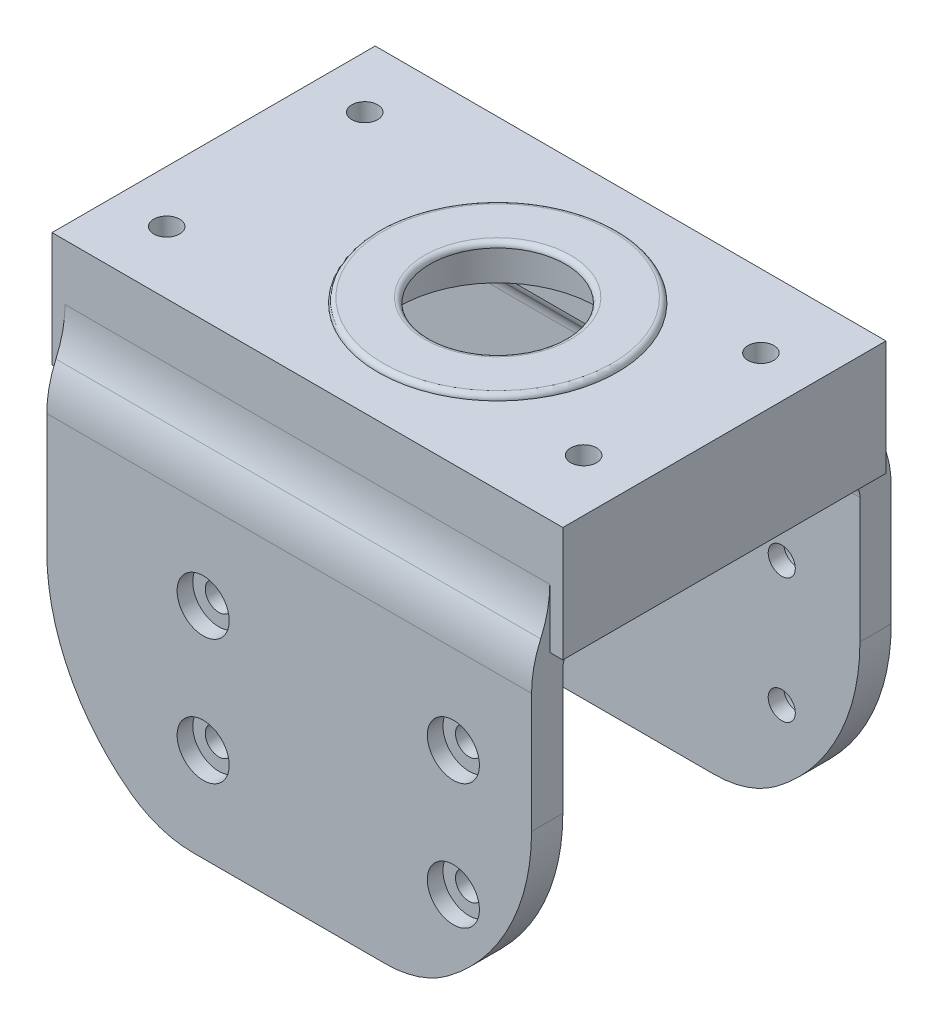
SolidWorks part; units mm, degrees
ref_plane "Front Plane" through (0, 0, 0) normal (0, 0, 1) x (1, 0, 0)
ref_plane "Top Plane" through (0, 0, 0) normal (0, 1, 0) x (1, 0, 0)
ref_plane "Right Plane" through (0, 0, 0) normal (1, 0, 0) x (0, 0, -1)
sketch "Sketch1" plane through (0, 0, 0) normal (0, 1, 0) x (1, 0, 0)
  line L0 (-24.5, 15.5) -> (24.5, 15.5)
  line L1 (-22.5, -13.5) -> (22.5, -13.5)
  line L2 (-22.5, -13.5) -> (-22.5, 13.5)
  line L3 (-22.5, 13.5) -> (22.5, 13.5)
  line L4 (22.5, -13.5) -> (22.5, 13.5)
  line L5 (-22.5, -13.5) -> (22.5, 13.5) construction
  line L6 (-22.5, 13.5) -> (22.5, -13.5) construction
  line L7 (24.5, -15.5) -> (24.5, 15.5)
  line L8 (-24.5, -15.5) -> (24.5, -15.5)
  line L9 (-24.5, -15.5) -> (-24.5, 15.5)
  circle A0 centre (2.75, 0) radius 9.475
  circle A1 centre (-19.5, 9.5) radius 1.24
  circle A2 centre (-19.5, -9.5) radius 1.24
  circle A3 centre (19.5, -8.5) radius 1.24
  circle A4 centre (19.5, 8.5) radius 1.24
  point P0 (0, 0)
  dimension "D4" = 18.95
  dimension "D6" = 2.48
  dimension "D1" = 45
  dimension "D2" = 27
  dimension "D5" = 25.25
  dimension "D7" = 3
  dimension "D8" = 4
  dimension "D9" = 4
  dimension "D10" = 3
  dimension "D11" = 5
  dimension "D12" = 5
  dimension "D3" = 2
extrude "Boss-Extrude1" add sketch "Sketch1" against normal blind 5 contours L1 L4 L3 L2 A0 region at (-21.9752, 0, 0)
extrude "Boss-Extrude2" add sketch "Sketch1<3>" against normal blind 11 contours L9 L8 L7 L0 L4 L1 L2 L3 region at (0, 0, -14.9202)
sketch "Sketch1<3>" plane through (0, 0, 0) normal (0, 1, 0) x (1, 0, 0) same geometry as "Sketch1"
sketch "Sketch2" plane through (0, -11, 0) normal (0, -1, 0) x (1, 0, 0)
  line L0 (-26.25, 17.25) -> (26.25, 17.25)
  line L1 (-23.25, -14.25) -> (23.25, -14.25)
  line L2 (-23.25, -14.25) -> (-23.25, 14.25)
  line L3 (-23.25, 14.25) -> (23.25, 14.25)
  line L4 (23.25, -14.25) -> (23.25, 14.25)
  line L5 (-23.25, -14.25) -> (23.25, 14.25) construction
  line L6 (-23.25, 14.25) -> (23.25, -14.25) construction
  line L7 (26.25, -17.25) -> (26.25, 17.25)
  line L8 (-26.25, -17.25) -> (26.25, -17.25)
  line L9 (-26.25, -17.25) -> (-26.25, 17.25)
  line L10 (-23.25, 14.25) -> (-23.25, 17.25)
  line L11 (23.25, 14.25) -> (23.25, 17.25)
  line L12 (23.25, -14.25) -> (23.25, -17.25)
  line L13 (-23.25, -14.25) -> (-23.25, -17.25)
  line L14 (-22.5, 13.5) -> (22.5, 13.5) construction
  line L15 (-15, 13.5) -> (15, 13.5)
  line L16 (-15, 13.5) -> (-15, 11.5)
  line L17 (-15, 11.5) -> (15, 11.5)
  line L18 (15, 13.5) -> (15, 11.5)
  line L19 (-22.5, -13.5) -> (22.5, -13.5) construction
  line L20 (-15, -13.5) -> (15, -13.5)
  line L21 (-15, -13.5) -> (-15, -11.5)
  line L22 (-15, -11.5) -> (15, -11.5)
  line L23 (15, -13.5) -> (15, -11.5)
  point P0 (0, 0)
  point P20 (0, 11.5)
  line M4 (-24.5, -15.5) -> (24.5, -15.5)
  line M6 (24.5, 15.5) -> (-24.5, 15.5)
  line M8 (22.5, -13.5) -> (-22.5, -13.5)
  line M10 (-22.5, 13.5) -> (22.5, 13.5)
  dimension "D1" = 46.5
  dimension "D2" = 28.5
  dimension "D4" = 30
  dimension "D5" = 2
  dimension "D3" = 3
extrude "Boss-Extrude3" add sketch "Sketch2" along normal blind 34 contours L11 L0 L10 M6 | L3 L11 L10 M6 | L1 L13 L12 M4 | L13 L8 L12 M4 region at (0, -11, 16.375) region at (0, -11, 14.875) region at (0, -11, -16.375) region at (0, -11, -14.875)
extrude "Boss-Extrude4" add sketch "Sketch2<4>" against normal up to next from offset 2 contours L18 L16 L17 M10 | L23 L22 L21 M8 region at (0, -11, 12.5) region at (0, -11, -12.5) offset against normal yes
sketch "Sketch2<4>" plane through (0, -11, 0) normal (0, -1, 0) x (1, 0, 0) same geometry as "Sketch2"
sketch "Sketch3" plane through (0, 0, -17.25) normal (0, 0, -1) x (-1, 0, 0)
  line L0 (23.25, -45) -> (23.25, -11) construction
  line L1 (23.25, -11) -> (-23.25, -11) construction
  circle A0 centre (-15.75, -22) radius 1.3
  circle A1 centre (8.25, -22) radius 1.3
  circle A2 centre (8.25, -34) radius 1.3
  circle A3 centre (-15.75, -34) radius 1.3
  circle A4 centre (-15.75, -22) radius 2.5
  circle A5 centre (-15.75, -34) radius 2.5
  circle A6 centre (8.25, -34) radius 2.5
  circle A7 centre (8.25, -22) radius 2.5
  dimension "D1" = 2.6
  dimension "D6" = 5
  dimension "D2" = 15
  dimension "D3" = 24
  dimension "D4" = 11
  dimension "D5" = 12
extrude "Cut-Extrude2" cut sketch "Sketch3" against normal through all contours A0 | A1 | A2 | A3 region at (15.75, -22, -17.25) region at (-8.25, -22, -17.25) region at (-8.25, -34, -17.25) region at (15.75, -34, -17.25)
extrude "Cut-Extrude3" cut sketch "Sketch3<3>" against normal blind 1.5
sketch "Sketch3<3>" plane through (0, 0, -17.25) normal (0, 0, -1) x (-1, 0, 0) same geometry as "Sketch3"
mirror "Mirror1" about plane through (0, 0, 0) normal (0, 0, 1) of "Cut-Extrude3"
fillet "Fillet3" radius 10 2 edges at (0, -11, -15.5) (0, -11, 15.5)
fillet "Fillet4" radius 10 2 edges at (0, -11, 17.25) (0, -11, -17.25)
fillet "Fillet5" radius 2 2 edges at (0, -11, 14.25) (0, -11, -14.25)
fillet "Fillet6" radius 2 2 edges at (0, -11.4388, -13.5) (0, -11.4388, 13.5)
fillet "Fillet7" radius 20 4 edges at (23.25, -45, 15.75) (-23.25, -45, 15.75) (-23.25, -45, -15.75) (23.25, -45, -15.75)
sketch "Sketch4" plane through (0, 0, 0) normal (0, 1, 0) x (1, 0, 0)
  circle A1 centre (2.75, 0) radius 6.5
  circle A2 centre (2.75, 0) radius 11.475
  circle A3 centre (2.75, 0) radius 11.475
  dimension "D2" = 13
  dimension "D1" = 2
extrude "Boss-Extrude5" add sketch "Sketch4" along normal blind 0.5
fillet "Fillet8" radius 0.5 2 edges at (2.75, 0.5, 11.475) (2.75, 0.5, 6.5)
sketch "Sketch5" plane through (0, 0, -17.25) normal (0, 0, -1) x (-1, 0, 0)
  line L0 (-11.9678, -43) -> (11.9678, -43)
  line L1 (3.25, -45) -> (-3.25, -45) construction
  line L2 (3.25, -45) -> (-3.25, -45)
  arc A0 (-23.25, -25) -> (-3.25, -45) centre (-3.25, -25) ccw construction
  arc A1 (3.25, -45) -> (23.25, -25) centre (3.25, -25) ccw construction
  arc A2 (-11.9678, -43) -> (-3.25, -45) centre (-3.25, -25) ccw
  arc A3 (3.25, -45) -> (11.9678, -43) centre (3.25, -25) ccw
  dimension "D1" = 2
extrude "Cut-Extrude4" cut sketch "Sketch5" against normal through all
fillet "Fillet9" radius 10 4 edges at (11.9678, -43, 15.75) (-11.9678, -43, 15.75) (-11.9678, -43, -15.75) (11.9678, -43, -15.75)
